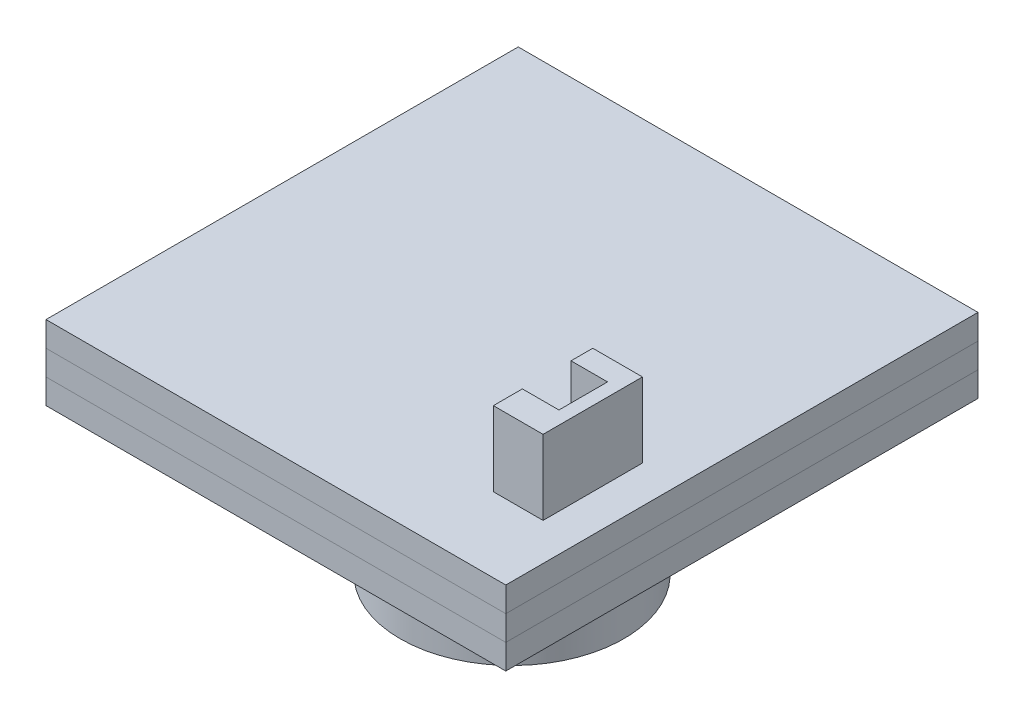
SolidWorks part; units mm, degrees
ref_plane "前视基准面" through (0, 0, 0) normal (0, 0, 1) x (1, 0, 0)
ref_plane "上视基准面" through (0, 0, 0) normal (0, 1, 0) x (1, 0, 0)
ref_plane "右视基准面" through (0, 0, 0) normal (1, 0, 0) x (0, 0, -1)
sketch "草图1" plane through (0, 0, 0) normal (0, 1, 0) x (1, 0, 0)
  line L0 (26.5, 0) -> (-26.5, 0) construction
  line L1 (-26.5, 19) -> (26.5, 19)
  line L2 (-26.5, 19) -> (-26.5, -19)
  line L3 (-26.5, -19) -> (26.5, -19)
  line L4 (26.5, 19) -> (26.5, -19)
  line L5 (-26.5, 19) -> (26.5, -19) construction
  line L6 (-26.5, -19) -> (26.5, 19) construction
  circle A0 centre (21.5, 7.5) radius 1.5
  circle A1 centre (21.5, -7.5) radius 1.5
  point P0 (0, 0)
  dimension "D3" = 3
  dimension "D4" = 5
  dimension "D5" = 15
  dimension "D1" = 38
  dimension "D2" = 53
extrude "凸台-拉伸1" add sketch "草图1" along normal blind 2
sketch "草图2" plane through (0, 2, 0) normal (0, 1, 0) x (1, 0, 0)
  line L0 (-26.5, -19) -> (26.5, -19) construction
  line L1 (-26.5, 19) -> (10.5, 19)
  line L2 (-26.5, 19) -> (-26.5, -19)
  line L3 (-26.5, -19) -> (10.5, -19)
  line L4 (10.5, 19) -> (10.5, -19)
  dimension "D1" = 37
extrude "凸台-拉伸2" add sketch "草图2" along normal blind 2 separate body
sketch "草图3" plane through (0, 4, 0) normal (0, 1, 0) x (1, 0, 0)
  line L4 (-26.5, 19) -> (-26.5, -19)
  line L5 (-26.5, -19) -> (10.5, -19)
  line L6 (10.5, -19) -> (10.5, 19)
  line L7 (10.5, 19) -> (-26.5, 19)
  line L8 (-26.5, 19) -> (-26.5, -19)
  line L9 (-26.5, -19) -> (10.5, -19)
  line L10 (10.5, -19) -> (10.5, 19)
  line L11 (10.5, 19) -> (-26.5, 19)
  dimension "D1" = 0
extrude "凸台-拉伸3" add sketch "草图3" along normal blind 2 separate body
sketch "草图4" plane through (0, 6, 0) normal (0, 1, 0) x (1, 0, 0)
  line L0 (-26.5, -19) -> (10.5, -19) construction
  line L1 (3.5, -13) -> (7.5, -13)
  line L2 (3.5, -13) -> (3.5, -5)
  line L3 (3.5, -5) -> (7.5, -5)
  line L4 (7.5, -13) -> (7.5, -5)
  line L5 (10.5, -19) -> (10.5, 19) construction
  line L7 (6.4412, -10.6649) -> (3.5, -10.6649)
  line L8 (6.4412, -10.6649) -> (6.4412, -6.7518)
  line L9 (6.4412, -6.7518) -> (3.5, -6.7518)
  line L10 (3.5, -10.6649) -> (3.5, -6.7518)
  line L11 (6.4412, -10.6649) -> (3.5, -6.7518) construction
  line L12 (6.4412, -6.7518) -> (3.5, -10.6649) construction
  point P8 (4.9706, -8.7084)
  dimension "D1" = 4
  dimension "D2" = 8
  dimension "D3" = 6
  dimension "D4" = 3
extrude "凸台-拉伸4" add sketch "草图4" along normal blind 6 contours L9 L8 L7 L2 L1 L4 L3 region at (3.5894, 6, 11.8325)
sketch "草图5" plane through (0, 0, 0) normal (0, -1, 0) x (1, 0, 0)
  line L0 (-8, -19) -> (-8, 19) construction
  line L1 (10.5, 0) -> (-26.5, 0) construction
  line L2 (-6, 10) -> (-6, 8)
  line L3 (-16, -8) -> (-10, -8)
  line L4 (-26.5, -19) -> (10.5, -19)
  line L5 (-26.5, 19) -> (-26.5, -19)
  line L6 (10.5, 19) -> (-26.5, 19)
  line L7 (10.5, -19) -> (10.5, 19)
  line L8 (-26.5, -19) -> (10.5, -19) construction
  line L9 (-26.5, 19) -> (-26.5, -19) construction
  line L10 (10.5, 19) -> (-26.5, 19) construction
  line L11 (10.5, -19) -> (10.5, 19) construction
  line L12 (-16, -8) -> (-16, 8)
  line L13 (-16, 8) -> (-10, 8)
  line L14 (0, -8) -> (0, 8)
  line L15 (-16, -8) -> (0, 8) construction
  line L16 (-16, 8) -> (0, -8) construction
  line L17 (-10, 10) -> (-10, 8)
  line L18 (-10, -10) -> (-10, -8)
  line L19 (-6, -10) -> (-6, -8)
  line L20 (-8, -8) -> (-6, -8) construction
  line L21 (-6, -8) -> (0, -8)
  line L22 (-10, -8) -> (-8, -8) construction
  line L23 (-8, 8) -> (-6, 8) construction
  line L24 (-6, 8) -> (0, 8)
  line L25 (-10, 8) -> (-8, 8) construction
  arc A0 (-6, 10) -> (-10, 10) centre (-8, 10) ccw
  circle A1 centre (-8, 10) radius 1
  circle A2 centre (-8, -10) radius 1
  arc A3 (-6, -10) -> (-10, -10) centre (-8, -10) cw
  arc A4 (-8, -8) -> (-6, -10) centre (-8, -10) cw construction
  arc A5 (-10, -10) -> (-8, -8) centre (-8, -10) cw construction
  arc A6 (-8, 8) -> (-6, 10) centre (-8, 10) ccw construction
  arc A7 (-10, 10) -> (-8, 8) centre (-8, 10) ccw construction
  point P8 (-8, 0)
  point P9 (-8, 0)
  dimension "D3" = 4
  dimension "D4" = 2
  dimension "D2" = 16
  dimension "D1" = 0
extrude "凸台-拉伸5" add sketch "草图5" along normal blind 4
sketch "草图6" plane through (0, -4, 0) normal (0, -1, 0) x (1, 0, 0)
  line L0 (-16, 8) -> (0, -8) construction
  line L1 (-16, -8) -> (-8, 0) construction
  circle A0 centre (-8, 0) radius 9
  dimension "D1" = 18
extrude "凸台-拉伸6" add sketch "草图6" along normal blind 8
sketch "草图7" plane through (0, -12, 0) normal (0, -1, 0) x (1, 0, 0)
  circle A0 centre (-8, 0) radius 6.6245
extrude "切除-拉伸1" cut sketch "草图7" against normal blind 2
ref_axis "基准轴1" through (-8, 8.2819, 0) along (0, -1, 0)
ref_plane "基准面1" through (-8, 0, 0) normal (1, 0, 0) x (0, -1, 0)
sketch "草图8" plane through (-8, 0, 0) normal (1, 0, 0) x (0, -1, 0)
  line L0 (10, 0) -> (11.7201, 0)
  line L1 (-8.2819, 0) -> (267.546, 0) construction
  line L2 (10, -6.6245) -> (10, 6.6245) construction
  line L3 (10, -6.6245) -> (10, 6.6245) construction
  line L4 (10, 0) -> (10, -6.6245)
  spline S0 degree 2 poles (10, -6.6245) (11.8598, -3.5864) (11.7201, 0) knots 0 0 0 1 1 1
revolve "旋转1" add sketch "草图8" angle 360 about L0
sketch "草图9" plane through (-8, 0, 0) normal (1, 0, 0) x (0, -1, 0)
  line L0 (6.2873, 0) -> (15.3777, 0) construction
  line L1 (-8.2819, 0) -> (267.546, 0) construction
  line L2 (4, -9) -> (12, -9) construction
  line L3 (6, -9) -> (7.5, -9)
  line L4 (6, -9) -> (6, -8.4234)
  line L5 (6.5, -7.9234) -> (7, -7.9234)
  line L6 (7.5, -9) -> (7.5, -8.4234)
  line L7 (4, -9) -> (4, 9) construction
  arc A0 (7, -7.9234) -> (7.5, -8.4234) centre (7, -8.4234) cw
  arc A1 (6, -8.4234) -> (6.5, -7.9234) centre (6.5, -8.4234) cw
  point P15 (7.5, -7.9234)
  point P18 (6, -7.9234)
  dimension "D3" = 0.5
  dimension "D1" = 1.5
  dimension "D2" = 2
revolve "切除-旋转1" cut sketch "草图9" angle 360 about L0
sketch "Sketch1" plane through (0, 2, 0) normal (0, 1, 0) x (1, 0, 0)
  line L0 (10.5, -19) -> (10.5, 19)
  line L4 (26.5, -19) -> (26.5, 19)
  line L5 (26.5, 19) -> (-26.5, 19)
  line L6 (-26.5, 19) -> (-26.5, -19)
  line L7 (-26.5, -19) -> (26.5, -19)
  line L8 (26.5, -19) -> (26.5, 19)
  line L9 (26.5, 19) -> (10.5, 19)
  line L11 (10.5, -19) -> (26.5, -19)
  dimension "D1" = 0
extrude "Cut-Extrude1" cut sketch "Sketch1" against normal blind 10
